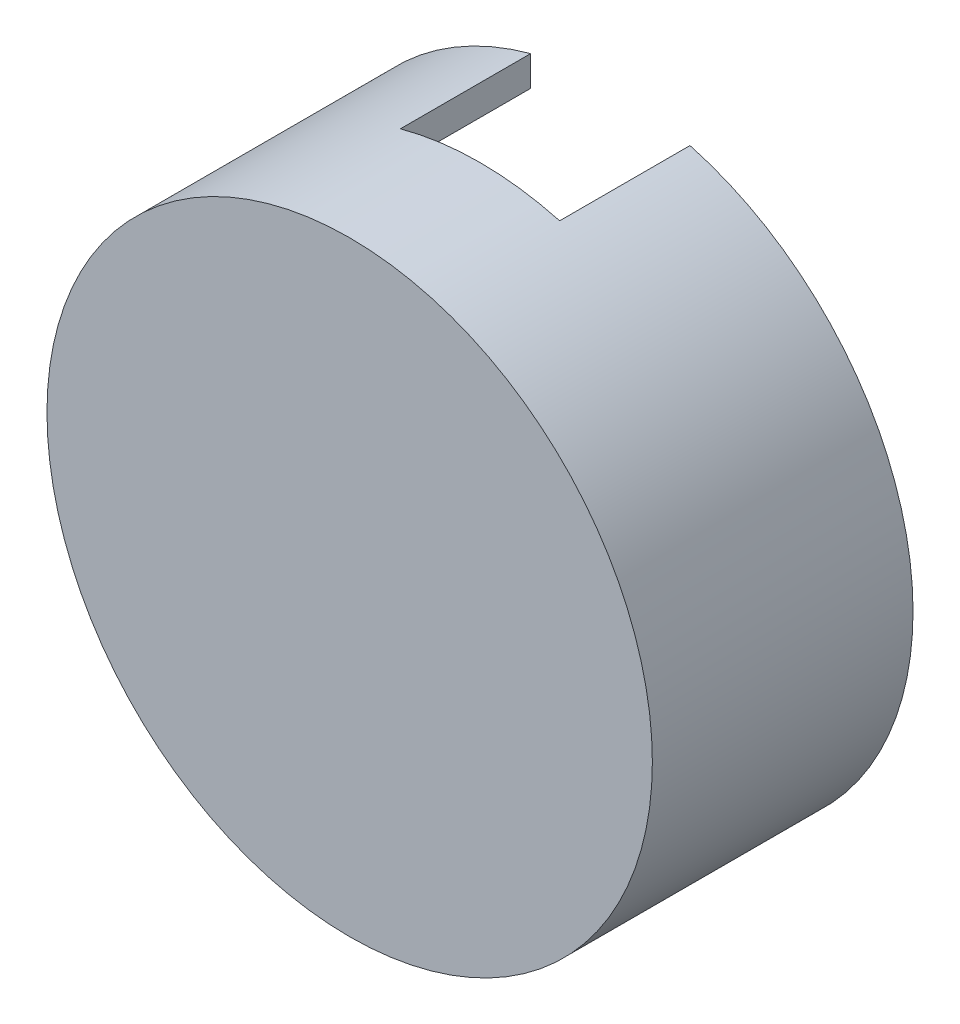
SolidWorks part; units mm, degrees
ref_plane "Ebene vorne" through (0, 0, 0) normal (0, 0, 1) x (1, 0, 0)
ref_plane "Ebene oben" through (0, 0, 0) normal (0, 1, 0) x (1, 0, 0)
ref_plane "Ebene rechts" through (0, 0, 0) normal (1, 0, 0) x (0, 0, -1)
sketch "Skizze1" plane through (0, 0, 0) normal (0, 1, 0) x (1, 0, 0)
  line L18 (0.0034, -8.0348) -> (0.0034, -10.0348)
  line L32 (20.9054, 7.9652) -> (18.9054, 7.9652)
  line L37 (0.0034, -10.0348) -> (20.9054, -10.0348)
  line L38 (0.0034, -8.0348) -> (18.9054, -8.0348)
  line L39 (20.9054, 7.9652) -> (20.9054, -10.0348)
  line L40 (18.9054, 7.9652) -> (18.9054, -2.0348)
  line L41 (18.9054, -2.0348) -> (17.4054, -2.0348)
  line L43 (17.4054, -4.0348) -> (18.9054, -4.0348)
  line L44 (18.9054, -4.0348) -> (18.9054, -8.0348)
  line L45 (17.4054, -2.0348) -> (17.4054, -4.0348)
revolve "Rotation2" add sketch "Skizze1" angle 360 about L18
sketch "Skizze2" plane through (0, 0, 0) normal (0, 1, 0) x (1, 0, 0)
  line L0 (-5.4966, 7.9652) -> (5.5034, 7.9652)
  line L1 (20.9054, 7.9652) -> (-20.8986, 7.9652) construction
  line L2 (-5.4966, -1.0348) -> (5.5034, -1.0348)
  line L3 (5.5034, 7.9652) -> (5.5034, -1.0348)
  line L4 (-5.4966, 7.9652) -> (-5.4966, -1.0348)
  dimension "D1" = 11
  dimension "D2" = 9
extrude "Schnitt-Linear austragen2" cut sketch "Skizze2" along normal blind 25 contours L2 L3 L0 L4
sketch "Skizze3" plane through (0, 0, 0) normal (1, 0, 0) x (0, 0, -1)
  line L4 (-2.03, 1.25) -> (-2.03, -1.25)
  line L5 (-2.03, -1.25) -> (0, -1.25)
  line L8 (0, -1.25) -> (0, 1.25)
  line L9 (0, 1.25) -> (-2.03, 1.25)
extrude "Aufsatz-Linear austragen1" add sketch "Skizze3" against normal blind 18.902
ref_plane "Ebene1" through (0, 1.25, 0) normal (0, 1, 0) x (1, 0, 0)
extrude "Schnitt-Linear austragen3" cut sketch "Skizze3<3>" against normal blind 16.402
sketch "Skizze3<3>" plane through (0, 0, 0) normal (1, 0, 0) x (0, 0, -1) same geometry as "Skizze3"
